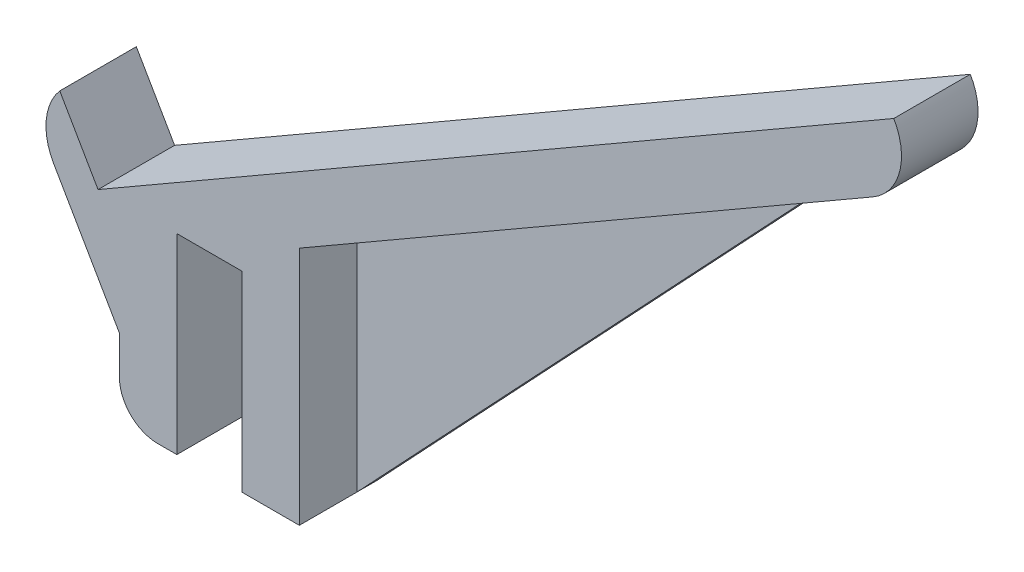
SolidWorks part; units mm, degrees
ref_plane "Front Plane" through (0, 0, 0) normal (0, 0, 1) x (1, 0, 0)
ref_plane "Top Plane" through (0, 0, 0) normal (0, 1, 0) x (1, 0, 0)
ref_plane "Right Plane" through (0, 0, 0) normal (1, 0, 0) x (0, 0, -1)
sketch "Sketch1" plane through (0, 0, 0) normal (0, 0, 1) x (1, 0, 0)
  line L0 (0, 0) -> (0, -50)
  line L1 (0, -50) -> (15, -50)
  line L2 (15, -50) -> (15, 12.7017)
  line L3 (15, 12.7017) -> (177.766, 106.6747)
  line L4 (0, 0) -> (-17, 0)
  line L5 (-17, 0) -> (-17, -50)
  line L6 (-17, -50) -> (-32, -50)
  line L7 (-32, -50) -> (-32, -30)
  line L8 (-32, -30) -> (-56.2404, 11.9856)
  line L9 (-56.2404, 11.9856) -> (-47.5801, 16.9856)
  line L10 (-47.5801, 16.9856) -> (-37.5801, -0.3349)
  line L11 (-37.5801, -0.3349) -> (170.266, 119.6651)
  line L12 (170.266, 119.6651) -> (177.766, 106.6747)
  line L13 (-17, -50) -> (0, -50) construction
  dimension "D1" = 17
  dimension "D2" = 15
  dimension "D3" = 15
  dimension "D4" = 15
  dimension "D5" = 10
  dimension "D6" = 240
  dimension "D7" = 50
  dimension "D8" = 20
  dimension "D9" = 30
  dimension "D10" = 20
  dimension "D11" = 10
extrude "Boss-Extrude1" add sketch "Sketch1" along normal blind 20
sketch "Sketch2" plane through (0, 0, 0) normal (0, 0, 1) x (1, 0, 0)
  line L0 (15, -50) -> (143.9853, 87.1714)
  line L1 (15, 12.7017) -> (177.766, 106.6747) construction
  line L2 (143.9853, 87.1714) -> (15, 12.7017)
  line L3 (15, 12.7017) -> (15, -50)
extrude "Boss-Extrude2" add sketch "Sketch2" along normal blind 5
fillet "Fillet1" radius 15 1 edges at (-56.2404, 11.9856, 10)
fillet "Fillet2" radius 10 1 edges at (-32, -50, 10)
fillet "Fillet3" radius 15 1 edges at (177.766, 106.6747, 10)
